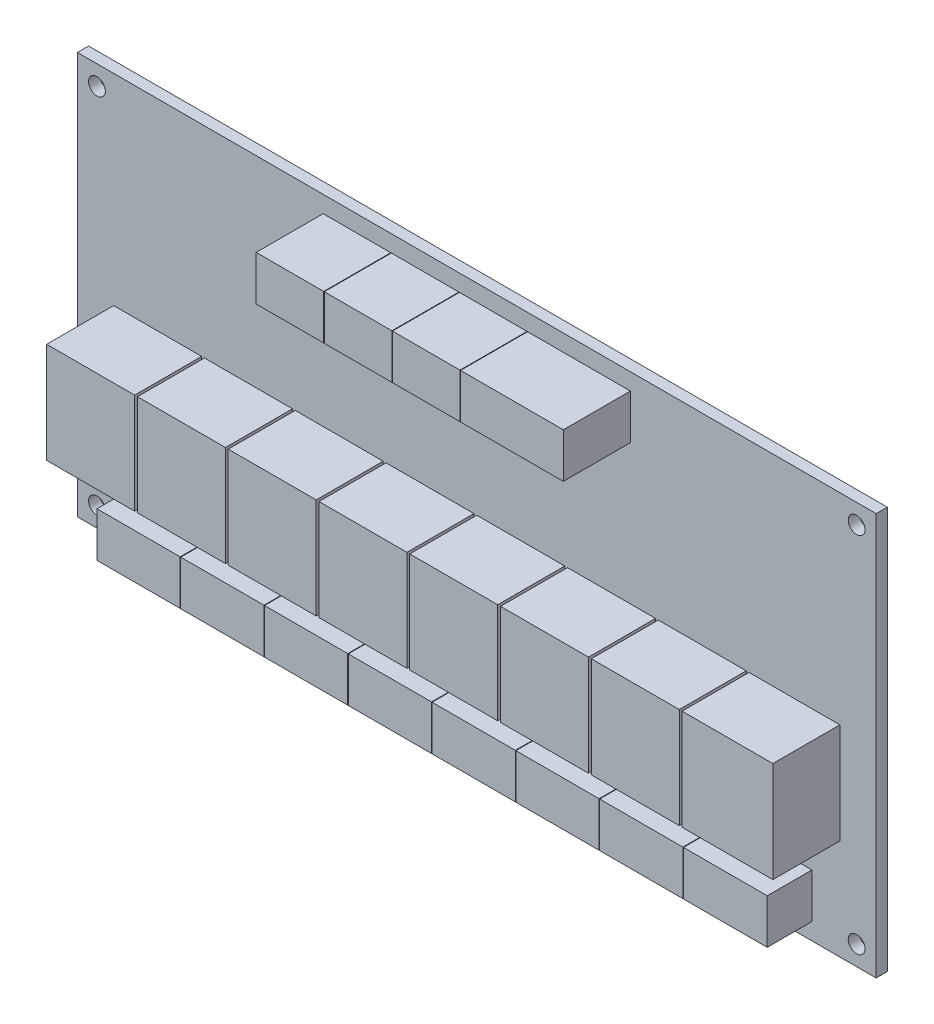
SolidWorks part; units mm, degrees
note: The reader was unsure of these and kept them because the rebuilt part matched: shared geometry of "草图3<3>", "草图3<4>".
ref_plane "前视基准面" through (0, 0, 0) normal (0, 0, 1) x (1, 0, 0)
ref_plane "上视基准面" through (0, 0, 0) normal (0, 1, 0) x (1, 0, 0)
ref_plane "右视基准面" through (0, 0, 0) normal (1, 0, 0) x (0, 0, -1)
sketch "草图1" plane through (0, 0, 0) normal (0, 0, 1) x (1, 0, 0)
  line L0 (0, 0) -> (143, 0)
  line L1 (0, 0) -> (0, 72)
  line L2 (0, 72) -> (143, 72)
  line L3 (143, 72) -> (143, 0)
extrude "凸台-拉伸1" add sketch "草图1" along normal blind 2
sketch "草图2" plane through (0, 0, 0) normal (0, 0, -1) x (-1, 0, 0)
  circle A0 centre (-139.5, 68.5) radius 1.5
  circle A1 centre (-139.5, 3.5) radius 1.5
  circle A2 centre (-3.5, 68.5) radius 1.5
  circle A3 centre (-3.5, 3.5) radius 1.5
extrude "切除-拉伸1" cut sketch "草图2" against normal blind 2
sketch "草图3" plane through (0, 0, 2) normal (0, 0, 1) x (1, 0, 0)
  line L0 (44, 61) -> (50.1, 61)
  line L1 (62.3, 61) -> (68.4, 61)
  line L2 (71.5, 3) -> (11.5, 3)
  line L3 (71.5, 3) -> (131.5, 3)
  line L4 (11.5, 3) -> (11.5, 11)
  line L5 (11.5, 11) -> (131.5, 11)
  line L6 (131.5, 11) -> (131.5, 3)
  line L7 (11.5, 3) -> (16.5, 3)
  line L8 (16.5, 3) -> (16.5, 11)
  line L9 (16.5, 3) -> (21.5, 3)
  line L10 (21.5, 3) -> (21.5, 11)
  line L11 (21.5, 3) -> (26.5, 3)
  line L12 (26.5, 3) -> (26.5, 11)
  line L13 (26.5, 3) -> (31.5, 3)
  line L14 (31.5, 3) -> (31.5, 11)
  line L15 (31.5, 3) -> (36.5, 3)
  line L16 (36.5, 3) -> (36.5, 11)
  line L17 (41.5, 3) -> (41.5, 11)
  line L18 (41.5, 3) -> (41.5, 11)
  line L19 (41.5, 3) -> (46.5, 3)
  line L20 (46.5, 3) -> (46.5, 11)
  line L21 (46.5, 3) -> (51.5, 3)
  line L22 (51.5, 3) -> (51.5, 11)
  line L23 (51.5, 3) -> (56.5, 3)
  line L24 (56.5, 3) -> (56.5, 11)
  line L25 (56.5, 3) -> (61.5, 3)
  line L26 (61.5, 3) -> (61.5, 11)
  line L27 (61.5, 3) -> (66.5, 3)
  line L28 (66.5, 3) -> (66.5, 11)
  line L29 (71.5, 3) -> (71.5, 11)
  line L30 (71.5, 3) -> (76.5, 3)
  line L31 (76.5, 3) -> (76.5, 11)
  line L32 (76.5, 3) -> (81.5, 3)
  line L33 (81.5, 3) -> (81.5, 11)
  line L34 (81.5, 3) -> (86.5, 3)
  line L35 (86.5, 3) -> (86.5, 11)
  line L36 (86.5, 3) -> (91.5, 3)
  line L37 (91.5, 3) -> (91.5, 11)
  line L38 (91.5, 3) -> (96.5, 3)
  line L39 (96.5, 3) -> (96.5, 11)
  line L40 (96.5, 3) -> (101.5, 3)
  line L41 (101.5, 3) -> (101.5, 11)
  line L42 (101.5, 3) -> (106.5, 3)
  line L43 (106.5, 3) -> (106.5, 11)
  line L44 (106.5, 3) -> (111.5, 3)
  line L45 (111.5, 3) -> (111.5, 11)
  line L46 (111.5, 3) -> (116.5, 3)
  line L47 (116.5, 3) -> (116.5, 11)
  line L48 (116.5, 3) -> (121.5, 3)
  line L49 (121.5, 3) -> (121.5, 11)
  line L50 (121.5, 3) -> (126.5, 3)
  line L51 (126.5, 3) -> (126.5, 11)
  line L52 (50.1, 61) -> (50.1, 69)
  line L53 (71.5, 18) -> (6.5, 18)
  line L54 (6.5, 18) -> (6.5, 36)
  line L55 (6.5, 36) -> (136.5, 36)
  line L56 (136.5, 36) -> (136.5, 18)
  line L57 (136.5, 18) -> (71.5, 18)
  line L58 (6.5, 36) -> (22.75, 36)
  line L59 (22.75, 36) -> (22.75, 18)
  line L60 (22.75, 36) -> (39, 36)
  line L61 (39, 36) -> (39, 18)
  line L62 (39, 36) -> (55.25, 36)
  line L63 (55.25, 36) -> (55.25, 18)
  line L64 (55.25, 36) -> (71.5, 36)
  line L65 (71.5, 36) -> (71.5, 18)
  line L66 (71.5, 36) -> (87.75, 36)
  line L67 (87.75, 36) -> (87.75, 18)
  line L68 (87.75, 36) -> (104, 36)
  line L69 (104, 36) -> (104, 18)
  line L70 (104, 36) -> (120.25, 36)
  line L71 (120.25, 36) -> (120.25, 18)
  line L72 (50.1, 61) -> (56.2, 61)
  line L73 (68.4, 61) -> (68.4, 69)
  line L74 (71.5, 69) -> (44, 69)
  line L75 (44, 69) -> (44, 61)
  line L76 (44, 61) -> (99, 61)
  line L77 (99, 61) -> (99, 69)
  line L78 (99, 69) -> (71.5, 69)
  line L79 (56.2, 61) -> (56.2, 69)
  line L80 (56.2, 61) -> (62.3, 61)
  line L81 (62.3, 61) -> (62.3, 69)
  line L82 (68.4, 61) -> (74.5, 61)
  line L83 (74.5, 61) -> (74.5, 69)
  line L84 (74.5, 61) -> (80.6, 61)
  line L85 (80.6, 61) -> (80.6, 69)
  line L86 (80.6, 61) -> (86.7, 61)
  line L87 (86.7, 61) -> (86.7, 69)
  line L88 (86.7, 61) -> (92.8, 61)
  line L89 (92.8, 61) -> (92.8, 69)
  line L90 (22.75, 36) -> (22.25, 36)
  line L91 (22.25, 36) -> (22.25, 18)
  line L92 (39, 36) -> (38.5, 36)
  line L93 (38.5, 36) -> (38.5, 18)
  line L94 (55.25, 36) -> (54.75, 36)
  line L95 (54.75, 36) -> (54.75, 18)
  line L96 (71.5, 36) -> (71, 36)
  line L97 (71, 36) -> (71, 18)
  line L98 (87.75, 36) -> (86.5, 36)
  line L99 (87.75, 36) -> (86.9858, 36)
  line L100 (104, 36) -> (103.5, 36)
  line L101 (103.5, 36) -> (103.5, 18)
  line L102 (120.25, 36) -> (119.75, 36)
  line L103 (119.75, 36) -> (119.75, 18)
  line L104 (87.75, 36) -> (87.25, 36)
  line L105 (87.25, 36) -> (87.25, 18)
  line L106 (26.5, 11) -> (26.1586, 11)
  line L107 (26.5, 11) -> (26.4, 11)
  line L108 (41.5, 11) -> (41.4, 11)
  line L109 (41.4, 11) -> (41.4, 3)
  line L110 (26.4, 11) -> (26.4, 3)
  line L111 (56.5, 11) -> (56.4, 11)
  line L112 (56.4, 11) -> (56.4, 3)
  line L113 (71.5, 11) -> (71.4, 11)
  line L114 (71.4, 11) -> (71.4, 3)
  line L115 (86.5, 11) -> (86.4, 11)
  line L116 (86.4, 11) -> (86.4, 3)
  line L117 (101.5, 11) -> (101.4, 11)
  line L118 (101.4, 11) -> (101.4, 3)
  line L119 (116.5, 11) -> (116.4, 11)
  line L120 (116.4, 11) -> (116.4, 3)
  line L121 (56.2, 69) -> (56.1, 69)
  line L122 (56.1, 69) -> (56.1, 61)
  line L123 (68.4, 69) -> (68.3, 69)
  line L124 (68.3, 69) -> (68.3, 61)
  line L125 (80.6, 69) -> (80.5, 69)
  line L126 (80.5, 69) -> (80.5, 61)
  dimension "D1" = 2
  dimension "D2" = 2
extrude "凸台-拉伸2" add sketch "草图3" along normal blind 8 contours L2 L8 L5 L4 | L2 L10 L5 L8 | L2 L12 L5 L10 | L2 L14 L5 L12 | L2 L16 L5 L14 | L2 L17 L5 L16 | L2 L20 L5 L17 | L2 L22 L5 L20 | L2 L24 L5 L22 | L2 L26 L5 L24 | L2 L28 L5 L26 | L2 L29 L5 L28 | L3 L31 L5 L29 | L3 L33 L5 L31 | L3 L35 L5 L33 | L3 L37 L5 L35 | L3 L39 L5 L37 | L3 L41 L5 L39 | L3 L43 L5 L41 | L3 L45 L5 L43 | L3 L47 L5 L45 | L3 L49 L5 L47 | L3 L51 L5 L49 | L51 L3 L6 L5
extrude "凸台-拉伸3" add sketch "草图3<3>" along normal blind 12
sketch "草图3<3>" plane through (0, 0, 2) normal (0, 0, 1) x (1, 0, 0) same geometry as "草图3"
extrude "凸台-拉伸4" add sketch "草图3<4>" along normal blind 12 contours L74 L75 L0 L52 | L122 L74 L52 L72 | L76 L81 L74 L79 | L124 L74 L81 L1 | L76 L83 L78 L74 L73 | L126 L78 L83 L76 | L76 L87 L78 L85 | L76 L89 L78 L87 | L89 L76 L77 L78
sketch "草图3<4>" plane through (0, 0, 2) normal (0, 0, 1) x (1, 0, 0) same geometry as "草图3"
